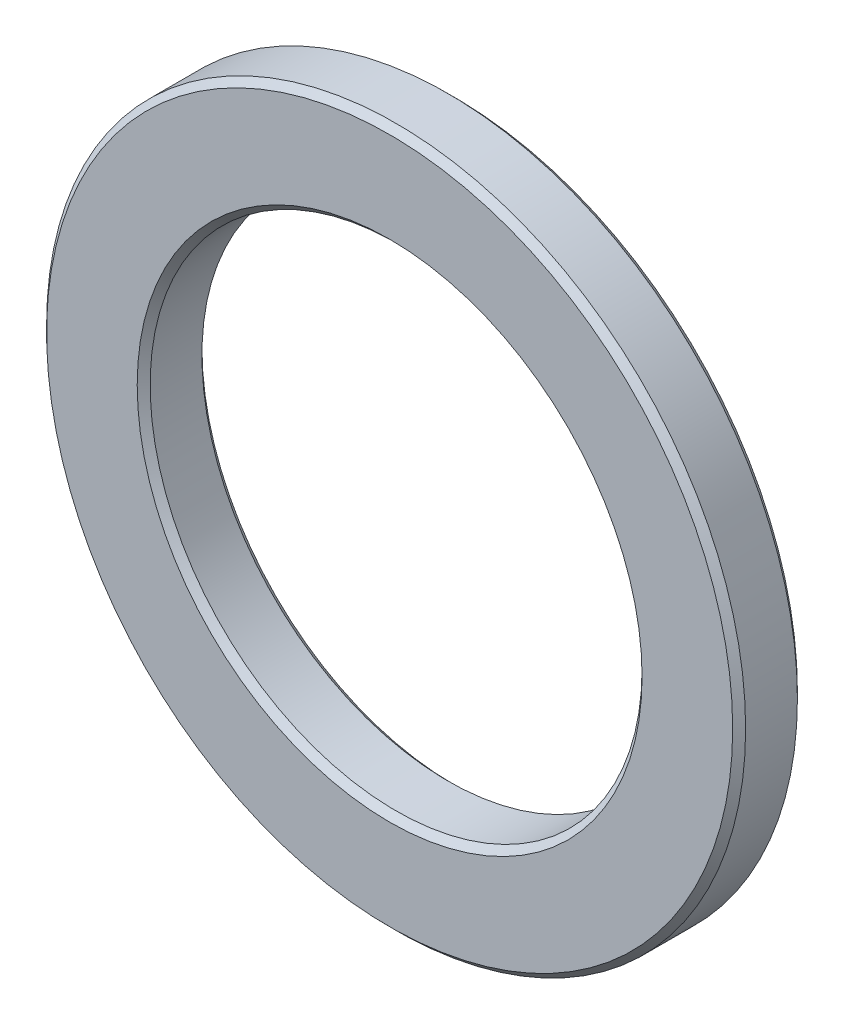
SolidWorks part; units mm, degrees
material "1.0037 (S235JR)"
ref_plane "E_Rechts" through (0, 0, 0) normal (0, 0, 1) x (1, 0, 0)
ref_plane "E_Oben" through (0, 0, 0) normal (0, 1, 0) x (1, 0, 0)
ref_plane "E_Vorne" through (0, 0, 0) normal (1, 0, 0) x (0, 0, -1)
ref_axis "A_Drehachse" through (0, 0, -88.99) along (0, 0, 1)
sketch "Skizze1" plane through (0, 0, 0) normal (0, 0, 1) x (1, 0, 0)
  circle A0 centre (0, 0) radius 19
  circle A1 centre (0, 0) radius 27
  dimension "D1" = 54
  dimension "D2" = 38
extrude "Aufsatz-Linear austragen1" add sketch "Skizze1" along normal mid plane 5
chamfer "Fase1" distance 0.5 angle 45 4 edges at (19, 0, -2.5) (27, 0, -2.5) (27, 0, 2.5) (19, 0, 2.5)
